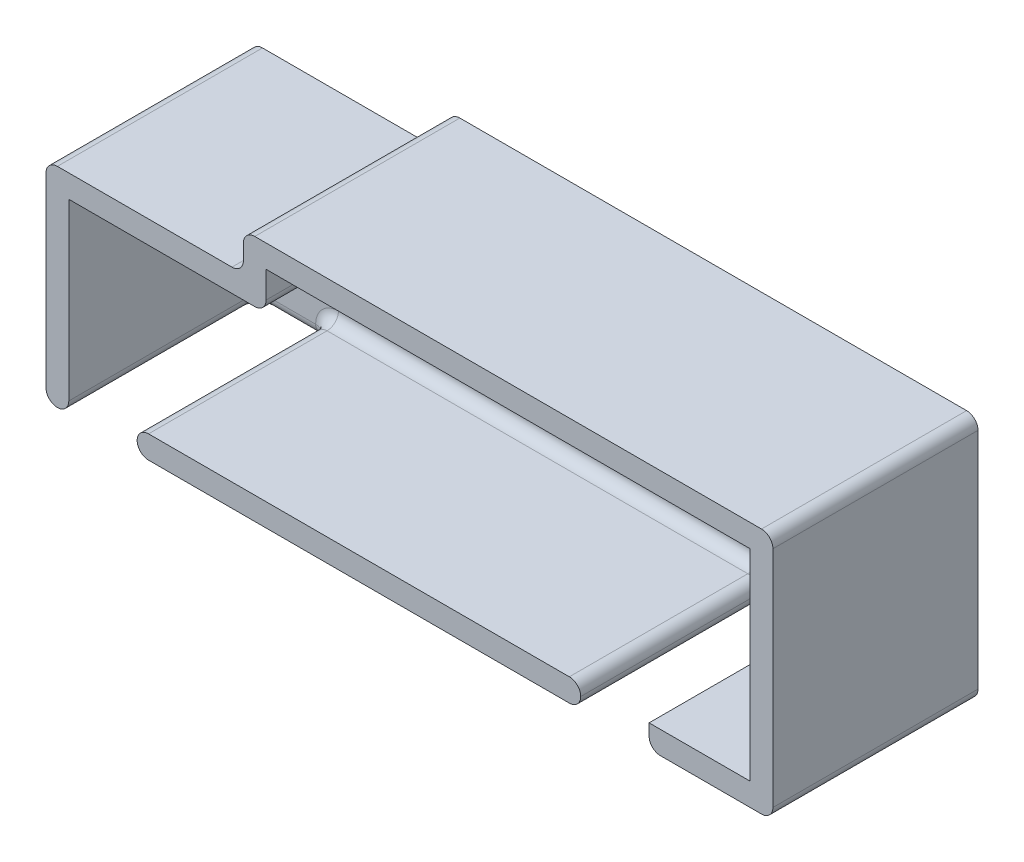
SolidWorks part; units mm, degrees
material "ABS"
ref_plane "X-Y Datum" through (0, 0, 0) normal (0, 0, 1) x (1, 0, 0)
ref_plane "X-Z Datum" through (0, 0, 0) normal (0, 1, 0) x (1, 0, 0)
ref_plane "Y-Z Datum" through (0, 0, 0) normal (1, 0, 0) x (0, 0, -1)
sketch "Sketch1" plane through (0, 0, -724.1914) normal (0, 0, 1) x (1, 0, 0)
  line L1 (476.4614, 467.0983) -> (476.4614, 412.0983)
  line L3 (476.4614, 412.0983) -> (285.0631, 412.0983)
  line L6 (285.0631, 467.0983) -> (285.0631, 412.0983)
  line L8 (285.0631, 467.0983) -> (337.0306, 467.0983)
  line L11 (476.4614, 467.0983) -> (476.4614, 477.0983)
  line L12 (476.4614, 477.0983) -> (337.0306, 477.0983)
  line L13 (337.0306, 467.0983) -> (337.0306, 477.0983)
  point P5 (485.0631, 411.5052)
  point P7 (476.4614, 412.0983)
  dimension "D1" = 191.3983
  dimension "D2" = 55
  dimension "D3" = 10
  dimension "D4" = 139.4307
  dimension "D5" = 191.3983
  dimension "D6" = 51.9675
extrude "Boss-Extrude1" add sketch "Sketch1" along normal blind 4
sketch "Sketch2" plane through (0, 0, -720.1914) normal (0, 0, 1) x (1, 0, 0)
  line L18 (343.0306, 461.0983) -> (291.0631, 461.0983)
  line L19 (291.0631, 461.0983) -> (291.0631, 418.0983)
  line L20 (291.0631, 418.0983) -> (470.4614, 418.0983)
  line L21 (470.4614, 418.0983) -> (470.4614, 471.0983)
  line L22 (343.0306, 461.0983) -> (291.0631, 461.0983)
  line L23 (291.0631, 461.0983) -> (291.0631, 418.0983)
  line L24 (291.0631, 418.0983) -> (470.4614, 418.0983)
  line L25 (470.4614, 418.0983) -> (470.4614, 471.0983)
  line L46 (343.0306, 471.0983) -> (343.0306, 461.0983)
  line L47 (343.0306, 471.0983) -> (343.0306, 461.0983)
  line L48 (470.4614, 471.0983) -> (343.0306, 471.0983)
  line L49 (470.4614, 471.0983) -> (343.0306, 471.0983)
  dimension "D1" = 6
extrude "Boss-Extrude2" add sketch "Sketch2" along normal blind 50
sketch "Sketch3" plane through (0, 0, -670.1914) normal (0, 0, 1) x (1, 0, 0)
  line L0 (291.0631, 418.0983) -> (470.4614, 418.0983) construction
  line L1 (291.0631, 418.0983) -> (470.4614, 418.0983)
  line L11 (470.4614, 418.0983) -> (470.4614, 471.0983) construction
  line L12 (343.0306, 461.0983) -> (291.0631, 461.0983) construction
  line L16 (285.0631, 412.0983) -> (476.4614, 412.0983) construction
  line L23 (443.858, 406.2672) -> (425.858, 406.2672)
  line L24 (443.858, 406.2672) -> (443.858, 427.5833)
  line L25 (443.858, 427.5833) -> (425.858, 427.5833)
  line L26 (425.858, 406.2672) -> (425.858, 427.5833)
  line L27 (291.0631, 418.0983) -> (309.0631, 418.0983)
  line L28 (291.0631, 418.0983) -> (291.0631, 412.0983)
  line L29 (291.0631, 412.0983) -> (309.0631, 412.0983)
  line L30 (309.0631, 418.0983) -> (309.0631, 412.0983)
  line L32 (476.4614, 477.0983) -> (337.0306, 477.0983)
  line L33 (337.0306, 477.0983) -> (337.0306, 467.0983)
  line L34 (337.0306, 467.0983) -> (285.0631, 467.0983)
  line L35 (285.0631, 467.0983) -> (285.0631, 412.0983)
  line L36 (285.0631, 412.0983) -> (476.4614, 412.0983)
  line L37 (476.4614, 412.0983) -> (476.4614, 477.0983)
  line L38 (476.4614, 477.0983) -> (337.0306, 477.0983)
  line L39 (337.0306, 477.0983) -> (337.0306, 467.0983)
  line L40 (337.0306, 467.0983) -> (285.0631, 467.0983)
  line L41 (285.0631, 467.0983) -> (285.0631, 412.0983)
  line L42 (285.0631, 412.0983) -> (476.4614, 412.0983)
  line L43 (476.4614, 412.0983) -> (476.4614, 477.0983)
  point P14 (294.1796, 411.2283)
  line M39 (285.0631, 412.0983) -> (476.4614, 412.0983)
  dimension "D1" = 26.6033
  dimension "D2" = 18
  dimension "D3" = 18
  dimension "D4" = 21.3161
  dimension "D5" = 33.515
  dimension "D6" = 0
extrude "Cut-Extrude1" cut sketch "Sketch3" against normal up to surface (50 mm away) and the other way through all contours L30 L1 L28 M39 | L26 L24 L1 M39 up to face at (368.185, 450.0983, -720.1914)
fillet "Fillet3" radius 3 23 edges at (343.0306, 461.0983, -695.1914) (337.0306, 477.0983, -697.1914) (337.0306, 467.0983, -697.1914) (285.0631, 467.0983, -697.1914) (476.4614, 477.0983, -697.1914) (476.4614, 412.0983, -697.1914) (285.0631, 412.0983, -697.1914) (291.0631, 412.0983, -695.1914) (434.858, 412.0983, -720.1914) (300.0631, 412.0983, -720.1914) (343.0306, 466.0983, -720.1914) (309.0631, 418.0983, -695.1914) (425.858, 418.0983, -695.1914) (443.858, 415.0983, -720.1914) (367.4606, 418.0983, -720.1914) (457.1597, 418.0983, -720.1914) (470.4614, 444.5983, -720.1914) (406.746, 471.0983, -720.1914) (317.0469, 461.0983, -720.1914) (291.0631, 436.5983, -720.1914) (309.0631, 412.0983, -695.1914) (443.858, 412.0983, -695.1914) (425.858, 412.0983, -695.1914)
